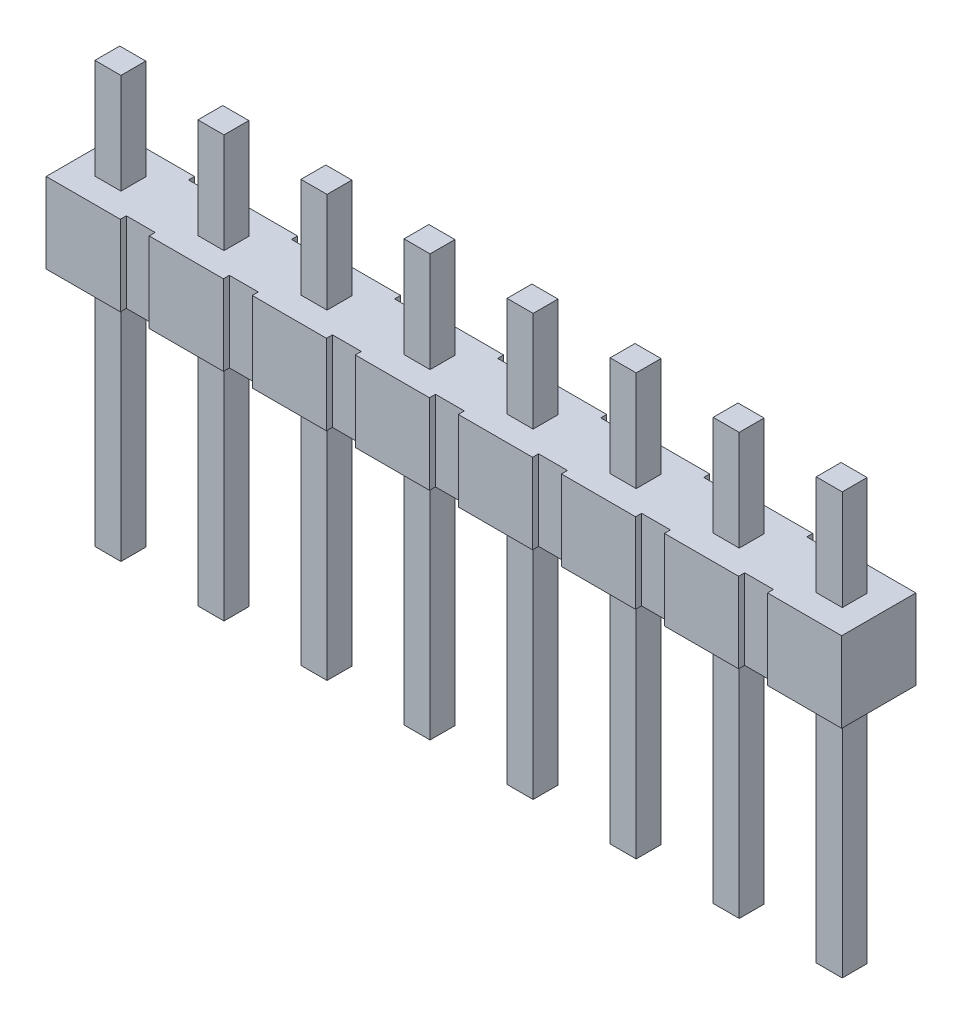
SolidWorks part; units mm, degrees
ref_plane "Front Plane" through (0, 0, 0) normal (0, 0, 1) x (1, 0, 0)
ref_plane "Top Plane" through (0, 0, 0) normal (0, 1, 0) x (1, 0, 0)
ref_plane "Right Plane" through (0, 0, 0) normal (1, 0, 0) x (0, 0, -1)
sketch "Sketch1" plane through (0, 0, 0) normal (0, 1, 0) x (1, 0, 0)
  line L0 (-9.75, 0.925) -> (-9.75, -0.925)
  line L1 (-10, 0.925) -> (10, 0.925) construction
  line L2 (-10, 0.925) -> (-10, -0.925) construction
  line L3 (-10, -0.925) -> (10, -0.925) construction
  line L4 (10, 0.925) -> (10, -0.925) construction
  line L5 (-10, 0.925) -> (10, -0.925) construction
  line L6 (-10, -0.925) -> (10, 0.925) construction
  line L7 (-9.75, -0.925) -> (-7.9, -0.925)
  line L8 (-7.9, -0.925) -> (-7.9, 0.925)
  line L9 (-7.9, 0.925) -> (-9.75, 0.925)
  line L10 (-9.75, 0.925) -> (-7.9, -0.925) construction
  line L11 (-9.75, -0.925) -> (-7.9, 0.925) construction
  line L12 (-6.58, 0.31) -> (-6.58, -0.31)
  line L13 (-9.15, 0.31) -> (-8.5, 0.31)
  line L14 (-9.15, 0.31) -> (-9.15, -0.31)
  line L15 (-9.15, -0.31) -> (-8.5, -0.31)
  line L16 (-8.5, 0.31) -> (-8.5, -0.31)
  line L17 (-9.15, 0.31) -> (-8.5, -0.31) construction
  line L18 (-9.15, -0.31) -> (-8.5, 0.31) construction
  line L19 (-6.58, 0.31) -> (-5.93, 0.31)
  line L20 (-5.93, 0.31) -> (-5.93, -0.31)
  line L21 (-6.58, -0.31) -> (-5.93, -0.31)
  line L22 (-7.18, 0.925) -> (-7.18, -0.925)
  line L23 (-5.33, 0.925) -> (-7.18, 0.925)
  line L24 (-5.33, -0.925) -> (-5.33, 0.925)
  line L25 (-7.18, -0.925) -> (-5.33, -0.925)
  line L26 (-4.01, 0.31) -> (-4.01, -0.31)
  line L27 (-4.01, 0.31) -> (-3.36, 0.31)
  line L28 (-3.36, 0.31) -> (-3.36, -0.31)
  line L29 (-4.01, -0.31) -> (-3.36, -0.31)
  line L30 (-4.61, 0.925) -> (-4.61, -0.925)
  line L31 (-2.76, 0.925) -> (-4.61, 0.925)
  line L32 (-2.76, -0.925) -> (-2.76, 0.925)
  line L33 (-4.61, -0.925) -> (-2.76, -0.925)
  line L34 (-1.44, 0.31) -> (-1.44, -0.31)
  line L35 (-1.44, 0.31) -> (-0.79, 0.31)
  line L36 (-0.79, 0.31) -> (-0.79, -0.31)
  line L37 (-1.44, -0.31) -> (-0.79, -0.31)
  line L38 (-2.04, 0.925) -> (-2.04, -0.925)
  line L39 (-0.19, 0.925) -> (-2.04, 0.925)
  line L40 (-0.19, -0.925) -> (-0.19, 0.925)
  line L41 (-2.04, -0.925) -> (-0.19, -0.925)
  line L42 (1.13, 0.31) -> (1.13, -0.31)
  line L43 (1.13, 0.31) -> (1.78, 0.31)
  line L44 (1.78, 0.31) -> (1.78, -0.31)
  line L45 (1.13, -0.31) -> (1.78, -0.31)
  line L46 (0.53, 0.925) -> (0.53, -0.925)
  line L47 (2.38, 0.925) -> (0.53, 0.925)
  line L48 (2.38, -0.925) -> (2.38, 0.925)
  line L49 (0.53, -0.925) -> (2.38, -0.925)
  line L50 (3.7, 0.31) -> (3.7, -0.31)
  line L51 (3.7, 0.31) -> (4.35, 0.31)
  line L52 (4.35, 0.31) -> (4.35, -0.31)
  line L53 (3.7, -0.31) -> (4.35, -0.31)
  line L54 (3.1, 0.925) -> (3.1, -0.925)
  line L55 (4.95, 0.925) -> (3.1, 0.925)
  line L56 (4.95, -0.925) -> (4.95, 0.925)
  line L57 (3.1, -0.925) -> (4.95, -0.925)
  line L58 (6.27, 0.31) -> (6.27, -0.31)
  line L59 (6.27, 0.31) -> (6.92, 0.31)
  line L60 (6.92, 0.31) -> (6.92, -0.31)
  line L61 (6.27, -0.31) -> (6.92, -0.31)
  line L62 (5.67, 0.925) -> (5.67, -0.925)
  line L63 (7.52, 0.925) -> (5.67, 0.925)
  line L64 (7.52, -0.925) -> (7.52, 0.925)
  line L65 (5.67, -0.925) -> (7.52, -0.925)
  line L66 (8.84, 0.31) -> (8.84, -0.31)
  line L67 (8.84, 0.31) -> (9.49, 0.31)
  line L68 (9.49, 0.31) -> (9.49, -0.31)
  line L69 (8.84, -0.31) -> (9.49, -0.31)
  line L70 (8.24, 0.925) -> (8.24, -0.925)
  line L71 (10.09, 0.925) -> (8.24, 0.925)
  line L72 (10.09, -0.925) -> (10.09, 0.925)
  line L73 (8.24, -0.925) -> (10.09, -0.925)
  line L74 (-9.15, 0.31) -> (-6.58, 0.31) construction
  line L75 (-7.9, 0.775) -> (-7.18, 0.775)
  line L76 (-7.9, -0.775) -> (-7.18, -0.775)
  line L77 (-5.33, 0.775) -> (-4.61, 0.775)
  line L78 (-5.33, -0.775) -> (-4.61, -0.775)
  line L79 (-2.76, 0.775) -> (-2.04, 0.775)
  line L80 (-2.76, -0.775) -> (-2.04, -0.775)
  line L81 (-0.19, 0.775) -> (0.53, 0.775)
  line L82 (-0.19, -0.775) -> (0.53, -0.775)
  line L83 (2.38, 0.775) -> (3.1, 0.775)
  line L84 (2.38, -0.775) -> (3.1, -0.775)
  line L85 (4.95, 0.775) -> (5.67, 0.775)
  line L86 (4.95, -0.775) -> (5.67, -0.775)
  line L87 (7.52, 0.775) -> (8.24, 0.775)
  line L88 (7.52, -0.775) -> (8.24, -0.775)
  line L89 (10.09, 0.775) -> (10.81, 0.775)
  line L90 (10.09, -0.775) -> (10.81, -0.775)
  line L91 (-7.9, 0.775) -> (-5.33, 0.775) construction
  point P0 (0, 0)
  point P8 (-8.825, 0)
  dimension "D1" = 20
  dimension "D2" = 1.85
  dimension "D3" = 0.25
  dimension "D4" = 1.85
  dimension "D5" = 0.65
  dimension "D6" = 0.62
  dimension "D8" = 2.57
  dimension "D9" = 0.15
  dimension "D10" = 0.15
  dimension "D12" = 2.57
  dimension "D7" = 8
  dimension "D11" = 8
extrude "Boss-Extrude1" add sketch "Sketch1" along normal blind 2 contours L8 L9 L0 L7 L13 L16 L15 L14 | L8 L76 L22 L75 | L22 L25 L24 L23 L21 L12 L19 L20 | L24 L78 L30 L77 | L30 L33 L32 L31 L29 L26 L27 L28 | L32 L80 L38 L79 | L38 L41 L40 L39 L37 L34 L35 L36 | L40 L82 L46 L81 | L46 L49 L48 L47 L45 L42 L43 L44 | L48 L84 L54 L83 | L54 L57 L56 L55 L53 L50 L51 L52 | L56 L86 L62 L85 | L62 L65 L64 L63 L61 L58 L59 L60 | L64 L88 L70 L87 | L70 L73 L72 L71 L69 L66 L67 L68 region at (-8.825, 0, -0.8988) region at (-7.54, 0, 0) region at (-7.1538, 0, -0.85) region at (-4.97, 0, 0) region at (-4.5838, 0, -0.85) region at (-2.4, 0, 0) region at (-2.0138, 0, -0.85) region at (0.17, 0, 0) region at (0.5562, 0, -0.85) region at (2.74, 0, 0) region at (3.1262, 0, -0.85) region at (5.31, 0, 0) region at (5.6962, 0, -0.85) region at (7.88, 0, 0) region at (8.2662, 0, -0.85)
extrude "Boss-Extrude2" add sketch "Sketch1<3>" along normal blind 4.5 and the other way blind 6 contours L16 L13 L14 L15 | L12 L21 L20 L19 | L26 L29 L28 L27 | L34 L37 L36 L35 | L42 L45 L44 L43 | L50 L53 L52 L51 | L58 L61 L60 L59 | L66 L69 L68 L67 region at (-6.255, 0, 0) region at (-8.825, 0, 0) region at (-3.685, 0, 0) region at (-1.115, 0, 0) region at (1.455, 0, 0) region at (4.025, 0, 0) region at (6.595, 0, 0) region at (9.165, 0, 0)
sketch "Sketch1<3>" plane through (0, 0, 0) normal (0, 1, 0) x (1, 0, 0) same geometry as "Sketch1"
